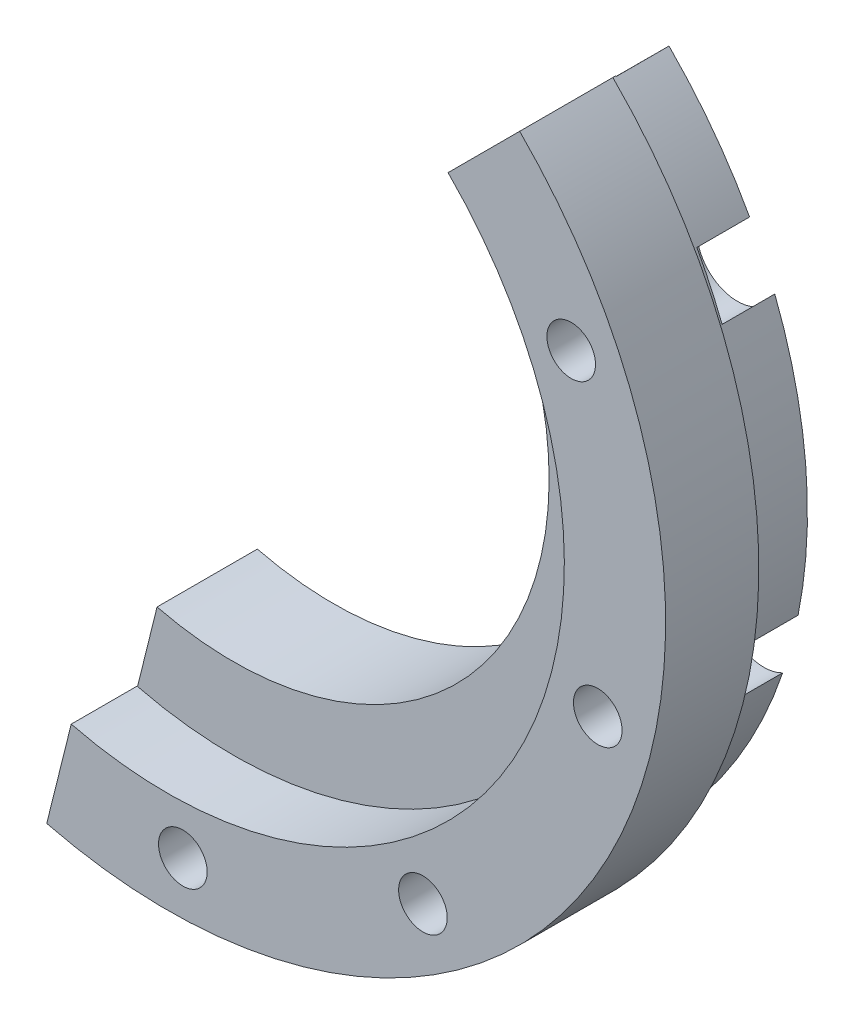
SolidWorks part; units mm, degrees
ref_plane "Front Plane" through (0, 0, 0) normal (0, 0, 1) x (1, 0, 0)
ref_plane "Top Plane" through (0, 0, 0) normal (0, 1, 0) x (1, 0, 0)
ref_plane "Right Plane" through (0, 0, 0) normal (1, 0, 0) x (0, 0, -1)
ref_plane "PZ_p24_600" through (0, 0, 24.6) normal (0, 0, 1) x (1, 0, 0)
sketch "S_prism1" plane through (0, 0, 24.6) normal (0, 0, 1) x (1, 0, 0)
  line L0 (-5.9513, -23.8693) -> (-4.7417, -19.0178)
  line L1 (13.8593, 13.8593) -> (17.3948, 17.3948)
  arc A0 (17.3948, 17.3948) -> (-5.9513, -23.8693) centre (0, 0) cw
  arc A1 (-4.7417, -19.0178) -> (13.8593, 13.8593) centre (0, 0) ccw
extrude "Boss_1" add sketch "S_prism1" along normal blind 5.6
ref_plane "PZ_p22_000" through (0, 0, 22) normal (0, 0, 1) x (1, 0, 0)
sketch "S_prism2" plane through (0, 0, 22) normal (0, 0, 1) x (1, 0, 0)
  line L0 (-5.6332, -22.7118) -> (-3.7555, -15.1412)
  line L1 (11.0443, 11.0174) -> (16.5665, 16.5261)
  arc A0 (16.5665, 16.5261) -> (-5.6332, -22.7118) centre (0, 0) cw
  arc A1 (-3.7555, -15.1412) -> (11.0443, 11.0174) centre (0, 0) ccw
extrude "Boss_2" add sketch "S_prism2" along normal blind 4.95
ref_plane "PZ_p24_500" through (0, 0, 24.5) normal (0, 0, 1) x (1, 0, 0)
sketch "S_pcut3" plane through (0, 0, 24.5) normal (0, 0, 1) x (1, 0, 0)
  line L0 (-6.4187, -23.955) -> (-6.0564, -22.6027)
  line L1 (16.255, 16.8326) -> (17.2275, 17.8396)
  arc A0 (17.2275, 17.8396) -> (-6.4187, -23.955) centre (0, 0) cw
  arc A1 (-6.0564, -22.6027) -> (16.255, 16.8326) centre (0, 0) ccw
extrude "Cut_3" cut sketch "S_pcut3" along normal blind 1.1
ref_plane "PZ_p21_900" through (0, 0, 21.9) normal (0, 0, 1) x (1, 0, 0)
sketch "S_hole4" plane through (0, 0, 21.9) normal (0, 0, 1) x (1, 0, 0)
  circle A0 centre (19.9388, 9.2976) radius 1.2
  dimension "D1_S_hole4" = 2.4
  dimension "P2" = 19.9388
  dimension "P3" = 9.2976
extrude "Hole_4" cut sketch "S_hole4" along normal blind 8.4
sketch "S_hole5" plane through (0, 0, 21.9) normal (0, 0, 1) x (1, 0, 0)
  circle A0 centre (19.9388, 9.2976) radius 2
  dimension "D1_S_hole5" = 4
  dimension "P2" = 19.9388
  dimension "P3" = 9.2976
extrude "Hole_5" cut sketch "S_hole5" along normal blind 2.7
sketch "S_hole6" plane through (0, 0, 21.9) normal (0, 0, 1) x (1, 0, 0)
  circle A0 centre (21.2504, -5.694) radius 1.2
  dimension "D1_S_hole6" = 2.4
  dimension "P2" = 21.2504
  dimension "P3" = 5.694
extrude "Hole_6" cut sketch "S_hole6" along normal blind 8.4
sketch "S_hole7" plane through (0, 0, 21.9) normal (0, 0, 1) x (1, 0, 0)
  circle A0 centre (21.2504, -5.694) radius 2
  dimension "D1_S_hole7" = 4
  dimension "P2" = 21.2504
  dimension "P3" = 5.694
extrude "Hole_7" cut sketch "S_hole7" along normal blind 2.7
sketch "S_hole8" plane through (0, 0, 21.9) normal (0, 0, 1) x (1, 0, 0)
  circle A0 centre (12.6187, -18.0213) radius 1.2
  dimension "D1_S_hole8" = 2.4
  dimension "P2" = 12.6187
  dimension "P3" = 18.0213
extrude "Hole_8" cut sketch "S_hole8" along normal blind 8.4
sketch "S_hole9" plane through (0, 0, 21.9) normal (0, 0, 1) x (1, 0, 0)
  circle A0 centre (12.6187, -18.0213) radius 2
  dimension "D1_S_hole9" = 4
  dimension "P2" = 12.6187
  dimension "P3" = 18.0213
extrude "Hole_9" cut sketch "S_hole9" along normal blind 2.7
sketch "S_hole10" plane through (0, 0, 21.9) normal (0, 0, 1) x (1, 0, 0)
  circle A0 centre (0.7678, -21.9866) radius 1.2
  dimension "D1_S_hole10" = 2.4
  dimension "P2" = 0.7678
  dimension "P3" = 21.9866
extrude "Hole_10" cut sketch "S_hole10" along normal blind 8.4
sketch "S_hole11" plane through (0, 0, 21.9) normal (0, 0, 1) x (1, 0, 0)
  circle A0 centre (0.7678, -21.9866) radius 2
  dimension "D1_S_hole11" = 4
  dimension "P2" = 0.7678
  dimension "P3" = 21.9866
extrude "Hole_11" cut sketch "S_hole11" along normal blind 2.7
equation "\"plate_t\" = 3"
equation "\"clearance\" = 0.4"
